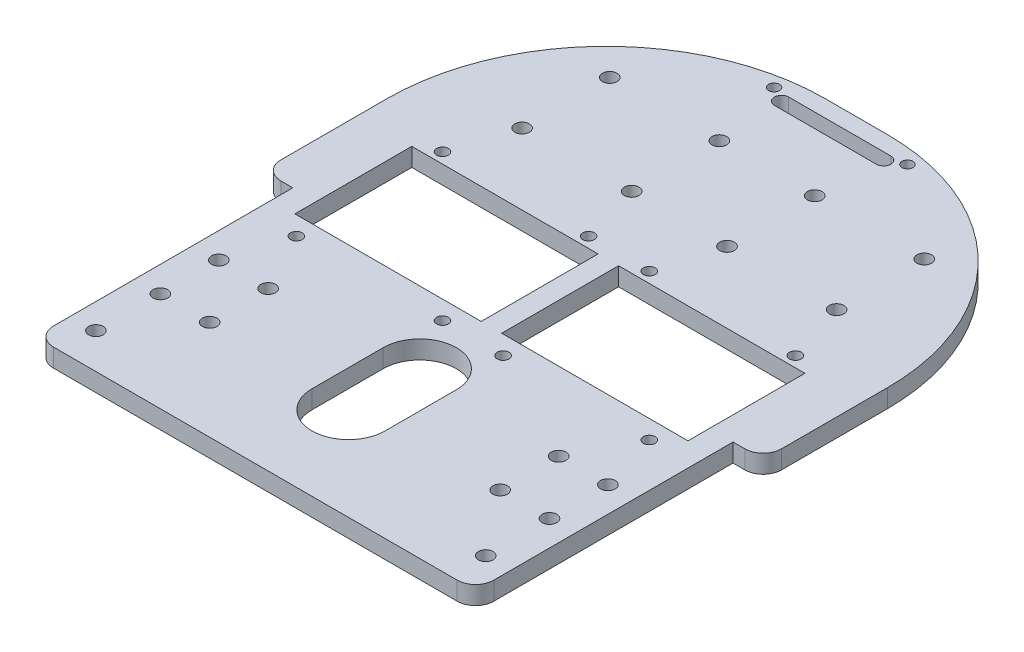
SolidWorks part; units mm, degrees
ref_plane "Front Plane" through (0, 0, 0) normal (0, 0, 1) x (1, 0, 0)
ref_plane "Top Plane" through (0, 0, 0) normal (0, 1, 0) x (1, 0, 0)
ref_plane "Right Plane" through (0, 0, 0) normal (1, 0, 0) x (0, 0, -1)
sketch "Sketch1" plane through (0, 0, 0) normal (0, 1, 0) x (1, 0, 0)
  line L0 (0, 90.99) -> (0, -94.01) construction
  line L1 (-94.5795, 0) -> (90.4205, 0) construction
  line L2 (-68.5, 80) -> (-68.5, -84.5)
  line L3 (-68.5, -84.5) -> (68.5, -84.5)
  line L4 (68.5, -84.5) -> (68.5, 80)
  line L5 (68.5, 80) -> (-68.5, 80)
  line L6 (-68.5, -14) -> (-68.5, -90)
  line L7 (-68.5, -90) -> (-60.25, -90)
  line L8 (-60.25, -90) -> (-60.25, -14)
  line L9 (-60.25, -14) -> (-68.5, -14)
  line L10 (60.25, -90) -> (60.25, -14)
  line L11 (68.5, -90) -> (60.25, -90)
  line L12 (68.5, -14) -> (68.5, -90)
  line L13 (60.25, -14) -> (68.5, -14)
  dimension "D1" = 60.25
  dimension "D2" = 68.5
  dimension "D3" = 80
  dimension "D4" = 185
  dimension "D5" = 185
  dimension "D6" = 84.5
  dimension "D7" = 76
  dimension "D8" = 94
  dimension "D9" = 68.5
extrude "Boss-Extrude2" add sketch "Sketch1" along normal blind 5 contours L10 L13 L4 L5 L2 L9 L8 L7 L3 L11 region at (0, 0, -0.308)
fillet "Fillet8" radius 60 2 edges at (68.5, 2.5, -80) (-68.5, 2.5, -80)
sketch "Sketch4" plane through (0, 5, 0) normal (0, 1, 0) x (1, 0, 0)
  line L0 (0, 0) -> (0, 80) construction
  line L1 (0, 80) -> (0, -84.5) construction
  line L2 (0, -39.5) -> (0, -59) construction
  line L3 (-68.5, 3) -> (68.5, 3) construction
  line L4 (-68.5, 20) -> (-68.5, -14) construction
  line L5 (68.5, -14) -> (68.5, 20) construction
  line L6 (-60.25, -84.5) -> (-60.25, -14) construction
  line L7 (8.5, 80) -> (-8.5, 80) construction
  line L8 (-60.25, -84.5) -> (60.25, -84.5) construction
  line L9 (60.25, -84.5) -> (60.25, -14) construction
  line L10 (-60.25, -49.25) -> (60.25, -49.25) construction
  line L13 (10, -39.5) -> (10, -59)
  line L16 (-10, -39.5) -> (-10, -59)
  line L17 (-53.7989, 12.1126) -> (-2.7989, 12.1126)
  line L18 (-2.7989, 12.1126) -> (-53.7989, 12.1126) construction
  line L19 (-53.7989, 12.1126) -> (-53.7989, -19.8874) construction
  line L20 (-2.7989, 12.1126) -> (-2.7989, -19.8874)
  line L21 (-2.7989, -19.8874) -> (-53.7989, -19.8874)
  line L22 (-53.7989, -19.8874) -> (-53.7989, 12.1126)
  line L23 (2.7989, -19.8874) -> (53.7989, -19.8874)
  line L24 (2.7989, 12.1126) -> (2.7989, -19.8874)
  line L25 (53.7989, 12.1126) -> (2.7989, 12.1126)
  line L26 (53.7989, -19.8874) -> (53.7989, 12.1126)
  line L27 (-13.9003, 73.4227) -> (14.0397, 73.4227) construction
  line L28 (-13.9003, 72.4027) -> (-13.9003, 74.4427) construction
  line L29 (14.0397, 72.4027) -> (14.0397, 74.4427) construction
  line L30 (-13.9003, 75.39) -> (14.0397, 75.39)
  line L31 (-13.9003, 71.4554) -> (14.0397, 71.4554)
  line L32 (-60.25, -84.5) -> (-60.25, -14) construction
  line L33 (-60.25, -84.5) -> (60.25, -84.5) construction
  circle A2 centre (-39.75, -41.25) radius 2
  circle A10 centre (39.75, -41.25) radius 2
  circle A13 centre (39.75, -57.25) radius 2
  circle A14 centre (-39.75, -57.25) radius 2
  circle A15 centre (-53.25, -41.25) radius 2
  circle A16 centre (-53.25, -57.25) radius 2
  circle A17 centre (53.25, -57.25) radius 2
  circle A18 centre (53.25, -41.25) radius 2
  arc A23 (10, -39.5) -> (-10, -39.5) centre (0, -39.5) ccw
  arc A24 (-10, -59) -> (10, -59) centre (0, -59) ccw
  circle A25 centre (-48.2989, 15.0126) radius 1.605
  circle A26 centre (-8.2989, 15.0126) radius 1.605
  circle A27 centre (-48.2989, -24.9874) radius 1.605
  circle A28 centre (-8.2989, -24.9874) radius 1.605
  circle A29 centre (48.2989, -24.9874) radius 1.605
  circle A30 centre (8.2989, -24.9874) radius 1.605
  circle A31 centre (8.2989, 15.0126) radius 1.605
  circle A32 centre (48.2989, 15.0126) radius 1.605
  circle A37 centre (13.0471, 55.5443) radius 2
  circle A38 centre (43.0471, 55.5443) radius 2
  circle A39 centre (43.0471, 31.5443) radius 2
  circle A40 centre (13.0471, 31.5443) radius 2
  circle A41 centre (-43.0471, 55.5443) radius 2
  circle A42 centre (-43.0471, 31.5443) radius 2
  circle A43 centre (-13.0471, 31.5443) radius 2
  circle A44 centre (-13.0471, 55.5443) radius 2
  circle A46 centre (-18.1803, 75.6527) radius 1.5
  circle A47 centre (18.3197, 75.6527) radius 1.5
  arc A48 (-13.9003, 75.39) -> (-13.9003, 71.4554) centre (-13.9003, 73.4227) ccw
  arc A49 (14.0397, 71.4554) -> (14.0397, 75.39) centre (14.0397, 73.4227) ccw
  circle A51 centre (-53.349, -74.7963) radius 2
  circle A52 centre (53.349, -74.7963) radius 2
  point P50 (0, -49.25)
  point P110 (0.0697, 73.4227)
  dimension "D2" = 4
  dimension "D13" = 4
  dimension "D10" = 7
  dimension "D11" = 20
  dimension "D5" = 3.21
  dimension "D6" = 4
  dimension "D7" = 3
  dimension "D3" = 16
  dimension "D4" = 16
  dimension "D8" = 3.9345
  dimension "D9" = 13.5
  dimension "D14" = 6.901
  dimension "D15" = 9.7037
  dimension "D16" = 19.5
extrude "Cut-Extrude1" cut sketch "Sketch4" against normal blind 5
fillet "Fillet17" radius 5 4 edges at (68.5, 2.5, 14) (60.25, 2.5, 84.5) (-60.25, 2.5, 84.5) (-68.5, 2.5, 14)
ref_plane "Plane1" through (60.25, 5, 14) normal (0, 0, -1) x (-1, 0, 0)
